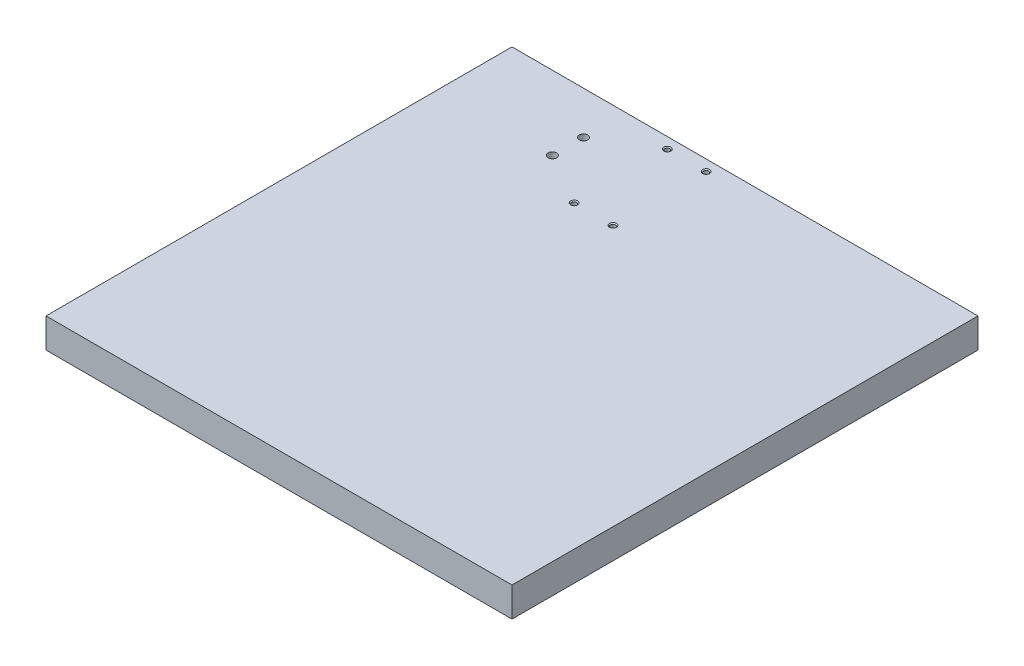
SolidWorks part; units mm, degrees
ref_plane "Front Plane" through (0, 0, 0) normal (0, 0, 1) x (1, 0, 0)
ref_plane "Top Plane" through (0, 0, 0) normal (0, 1, 0) x (1, 0, 0)
ref_plane "Right Plane" through (0, 0, 0) normal (1, 0, 0) x (0, 0, -1)
sketch "Sketch1" plane through (0, 0, 0) normal (0, 1, 0) x (1, 0, 0)
  line L1 (0, 0) -> (300, 0)
  line L2 (0, 0) -> (0, 300)
  line L3 (0, 300) -> (300, 300)
  line L4 (300, 0) -> (300, 300)
  dimension "D1" = 300
  dimension "D2" = 300
extrude "Boss-Extrude1" add sketch "Sketch1" along normal blind 19.05
hole_wizard "M4 Tapped Hole1" positions "Sketch3" profile "Sketch2" tap size "M4" standard "ISO"
sketch "Sketch3" plane through (0, 19.05, 0) normal (0, 1, 0) x (-1, 0, 0)
  line L0 (0, -300) -> (0, 0) construction
  line L1 (-300, -300) -> (0, -300) construction
  point P0 (-107, -293)
  point P1 (-132, -293)
  point P3 (-132, -233)
  point P5 (-107, -233)
  dimension "D1" = 107
  dimension "D2" = 7
  dimension "D3" = 25
  dimension "D4" = 60
sketch "Sketch2" plane through (107, 19.05, -293) normal (1, 0, 0) x (0, 0, 1)
  line L0 (0, 0) -> (0, 75.9914)
  line L1 (0, 75.9914) -> (1.65, 75)
  line L2 (1.65, 75) -> (1.65, 0.6)
  line L3 (1.65, 0.6) -> (2.25, 0)
  line L5 (2.25, 0) -> (0, 0)
  line L6 (-1.65, 0.6) -> (-2.25, 0) construction
  line L10 (0, 75.9914) -> (-1.65, 75) construction
  line L11 (0, -6.35) -> (0, 107.95) construction
  dimension "Tap Drill Dia." = 3.3
  dimension "Tap Drill Depth" = 75
  dimension "Near C'Sink Dia." = 4.5
  dimension "Near C'Sink Angle" = 90
  dimension "Drill Angle" = 118
cosmetic thread "Hole Thread1" parameters "D1"=8, "D2"=4
cosmetic thread "Hole Thread2" parameters "D1"=8, "D2"=4
cosmetic thread "Hole Thread3" parameters "D1"=8, "D2"=4
cosmetic thread "Hole Thread4" parameters "D1"=8, "D2"=4
hole_wizard "CBORE for M5 Hex Socket Head Cap Screw1" positions "Sketch5" profile "Sketch6" counterbore size "M5" standard "ISO" end condition through all
sketch "Sketch5" plane through (0, 0, 0) normal (0, -1, 0) x (1, 0, 0)
  line L0 (300, -300) -> (0, -300) construction
  line L1 (0, -300) -> (0, 0) construction
  point P0 (73.5, -272.5)
  point P1 (73.5, -252.5)
  dimension "D1" = 27.5
  dimension "D2" = 73.5
  dimension "D3" = 20
sketch "Sketch6" plane through (73.5, 0, -272.5) normal (1, 0, 0) x (0, 0, -1)
  line L0 (0, 0) -> (0, 19.05)
  line L1 (0, 19.05) -> (2.75, 19.05)
  line L3 (2.75, 19.05) -> (2.75, 5)
  line L4 (2.75, 5) -> (5, 5)
  line L5 (5, 5) -> (5, 0)
  line L7 (5, 0) -> (0, 0)
  line L11 (0, -6.35) -> (0, 107.95) construction
  dimension "Thru Hole Dia." = 5.5
  dimension "Thru Hole Depth" = 19.05
  dimension "C'Bore Dia." = 10
  dimension "C'Bore Depth" = 5
